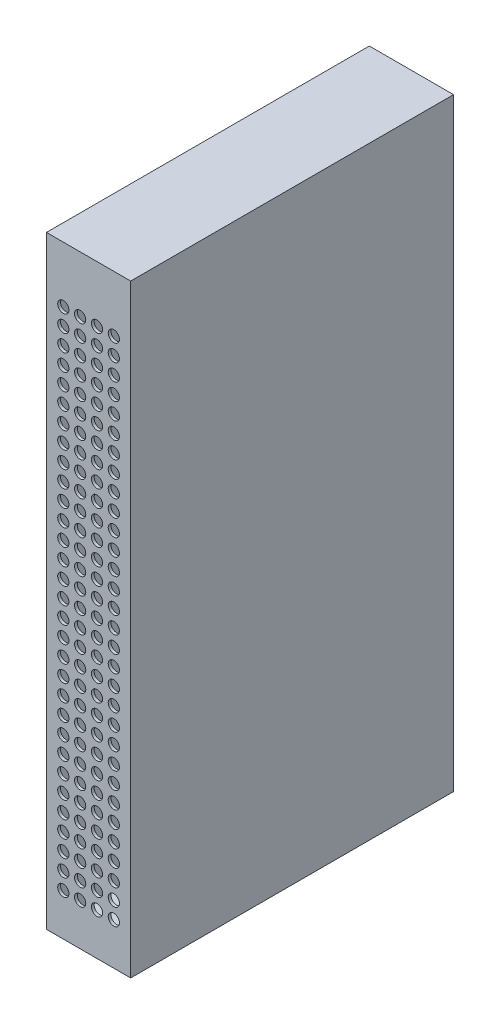
SolidWorks part; units mm, degrees
ref_plane "Front Plane" through (0, 0, 0) normal (0, 0, 1) x (1, 0, 0)
ref_plane "Top Plane" through (0, 0, 0) normal (0, 1, 0) x (1, 0, 0)
ref_plane "Right Plane" through (0, 0, 0) normal (1, 0, 0) x (0, 0, -1)
sketch "Sketch1" plane through (0, 0, 0) normal (0, 0, 1) x (1, 0, 0)
  line L1 (-15, 0) -> (15, 0)
  line L2 (-15, 0) -> (-15, 215)
  line L3 (-15, 215) -> (15, 215)
  line L4 (15, 0) -> (15, 215)
extrude "Case" add sketch "Sketch1" along normal blind 115
shell "Case_shell" thickness 1
ref_plane "Plane_z115" through (0, 0, 115) normal (0, 0, 1) x (1, 0, 0)
sketch "Sketch2" plane through (0, 0, 115) normal (0, 0, 1) x (1, 0, 0)
  circle A0 centre (-9, 15) radius 2
  circle A1 centre (-9, 21) radius 2
  circle A2 centre (-9, 27) radius 2
  circle A3 centre (-9, 33) radius 2
  circle A4 centre (-9, 39) radius 2
  circle A5 centre (-9, 45) radius 2
  circle A6 centre (-9, 51) radius 2
  circle A7 centre (-9, 57) radius 2
  circle A8 centre (-9, 63) radius 2
  circle A9 centre (-9, 69) radius 2
  circle A10 centre (-9, 75) radius 2
  circle A11 centre (-9, 81) radius 2
  circle A12 centre (-9, 87) radius 2
  circle A13 centre (-9, 93) radius 2
  circle A14 centre (-9, 99) radius 2
  circle A15 centre (-9, 105) radius 2
  circle A16 centre (-9, 111) radius 2
  circle A17 centre (-9, 117) radius 2
  circle A18 centre (-9, 123) radius 2
  circle A19 centre (-9, 129) radius 2
  circle A20 centre (-9, 135) radius 2
  circle A21 centre (-9, 141) radius 2
  circle A22 centre (-9, 147) radius 2
  circle A23 centre (-9, 153) radius 2
  circle A24 centre (-9, 159) radius 2
  circle A25 centre (-9, 165) radius 2
  circle A26 centre (-9, 171) radius 2
  circle A27 centre (-9, 177) radius 2
  circle A28 centre (-9, 183) radius 2
  circle A29 centre (-9, 189) radius 2
  circle A30 centre (-9, 195) radius 2
  circle A31 centre (-3, 15) radius 2
  circle A32 centre (-3, 21) radius 2
  circle A33 centre (-3, 27) radius 2
  circle A34 centre (-3, 33) radius 2
  circle A35 centre (-3, 39) radius 2
  circle A36 centre (-3, 45) radius 2
  circle A37 centre (-3, 51) radius 2
  circle A38 centre (-3, 57) radius 2
  circle A39 centre (-3, 63) radius 2
  circle A40 centre (-3, 69) radius 2
  circle A41 centre (-3, 75) radius 2
  circle A42 centre (-3, 81) radius 2
  circle A43 centre (-3, 87) radius 2
  circle A44 centre (-3, 93) radius 2
  circle A45 centre (-3, 99) radius 2
  circle A46 centre (-3, 105) radius 2
  circle A47 centre (-3, 111) radius 2
  circle A48 centre (-3, 117) radius 2
  circle A49 centre (-3, 123) radius 2
  circle A50 centre (-3, 129) radius 2
  circle A51 centre (-3, 135) radius 2
  circle A52 centre (-3, 141) radius 2
  circle A53 centre (-3, 147) radius 2
  circle A54 centre (-3, 153) radius 2
  circle A55 centre (-3, 159) radius 2
  circle A56 centre (-3, 165) radius 2
  circle A57 centre (-3, 171) radius 2
  circle A58 centre (-3, 177) radius 2
  circle A59 centre (-3, 183) radius 2
  circle A60 centre (-3, 189) radius 2
  circle A61 centre (-3, 195) radius 2
  circle A62 centre (3, 15) radius 2
  circle A63 centre (3, 21) radius 2
  circle A64 centre (3, 27) radius 2
  circle A65 centre (3, 33) radius 2
  circle A66 centre (3, 39) radius 2
  circle A67 centre (3, 45) radius 2
  circle A68 centre (3, 51) radius 2
  circle A69 centre (3, 57) radius 2
  circle A70 centre (3, 63) radius 2
  circle A71 centre (3, 69) radius 2
  circle A72 centre (3, 75) radius 2
  circle A73 centre (3, 81) radius 2
  circle A74 centre (3, 87) radius 2
  circle A75 centre (3, 93) radius 2
  circle A76 centre (3, 99) radius 2
  circle A77 centre (3, 105) radius 2
  circle A78 centre (3, 111) radius 2
  circle A79 centre (3, 117) radius 2
  circle A80 centre (3, 123) radius 2
  circle A81 centre (3, 129) radius 2
  circle A82 centre (3, 135) radius 2
  circle A83 centre (3, 141) radius 2
  circle A84 centre (3, 147) radius 2
  circle A85 centre (3, 153) radius 2
  circle A86 centre (3, 159) radius 2
  circle A87 centre (3, 165) radius 2
  circle A88 centre (3, 171) radius 2
  circle A89 centre (3, 177) radius 2
  circle A90 centre (3, 183) radius 2
  circle A91 centre (3, 189) radius 2
  circle A92 centre (3, 195) radius 2
  circle A93 centre (9, 15) radius 2
  circle A94 centre (9, 21) radius 2
  circle A95 centre (9, 27) radius 2
  circle A96 centre (9, 33) radius 2
  circle A97 centre (9, 39) radius 2
  circle A98 centre (9, 45) radius 2
  circle A99 centre (9, 51) radius 2
  circle A100 centre (9, 57) radius 2
  circle A101 centre (9, 63) radius 2
  circle A102 centre (9, 69) radius 2
  circle A103 centre (9, 75) radius 2
  circle A104 centre (9, 81) radius 2
  circle A105 centre (9, 87) radius 2
  circle A106 centre (9, 93) radius 2
  circle A107 centre (9, 99) radius 2
  circle A108 centre (9, 105) radius 2
  circle A109 centre (9, 111) radius 2
  circle A110 centre (9, 117) radius 2
  circle A111 centre (9, 123) radius 2
  circle A112 centre (9, 129) radius 2
  circle A113 centre (9, 135) radius 2
  circle A114 centre (9, 141) radius 2
  circle A115 centre (9, 147) radius 2
  circle A116 centre (9, 153) radius 2
  circle A117 centre (9, 159) radius 2
  circle A118 centre (9, 165) radius 2
  circle A119 centre (9, 171) radius 2
  circle A120 centre (9, 177) radius 2
  circle A121 centre (9, 183) radius 2
  circle A122 centre (9, 189) radius 2
  circle A123 centre (9, 195) radius 2
extrude "Perforation" cut sketch "Sketch2" against normal blind 1
